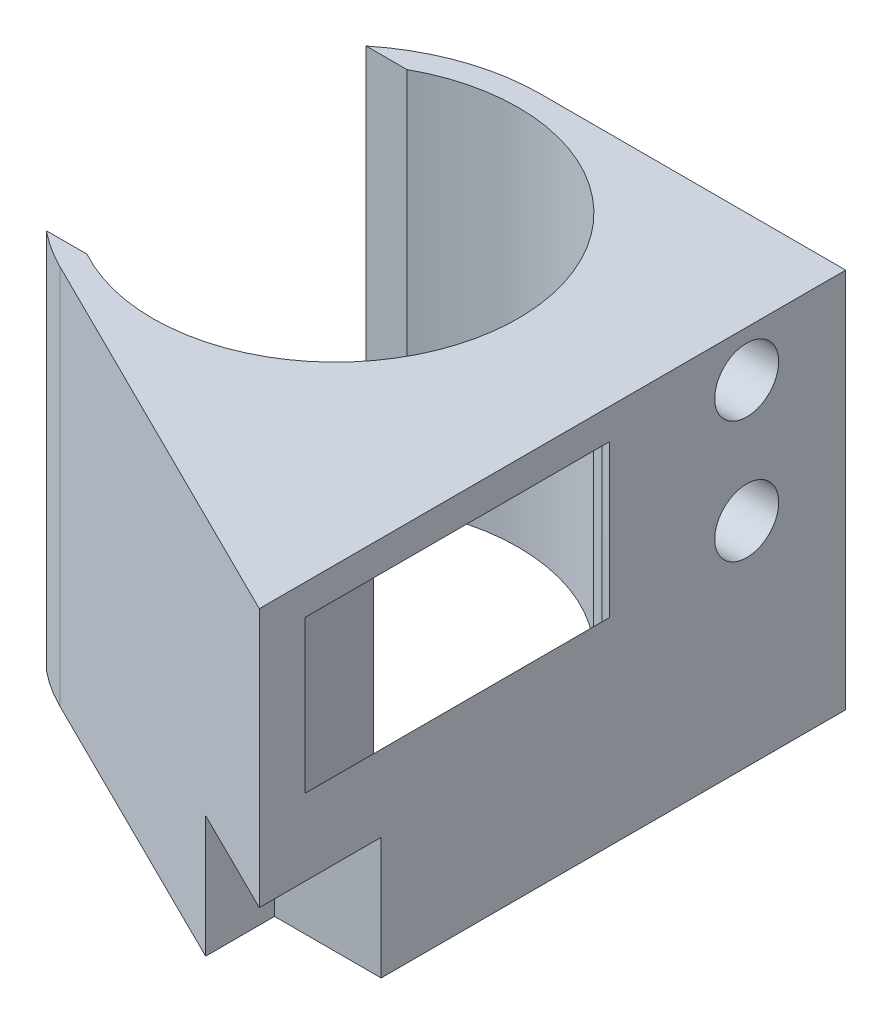
SolidWorks part; units mm, degrees
ref_plane "Front Plane" through (0, 0, 0) normal (0, 0, 1) x (1, 0, 0)
ref_plane "Top Plane" through (0, 0, 0) normal (0, 1, 0) x (1, 0, 0)
ref_plane "Right Plane" through (0, 0, 0) normal (1, 0, 0) x (0, 0, -1)
sketch "Sketch1" plane through (0, 0, 0) normal (0, 1, 0) x (1, 0, 0)
  line L0 (0, 13.5) -> (20, 13.5)
  line L1 (20, 13.5) -> (20, -25)
  line L2 (20, -25) -> (-6.0026, -12.0921)
  line L3 (0, 0) -> (20, 0) construction
  line L4 (20, 0) -> (20, -25) construction
  circle A0 centre (0, 0) radius 12
  arc A1 (0, 13.5) -> (-6.0026, -12.0921) centre (0, 0) ccw
  dimension "D1" = 24
  dimension "D2" = 27
  dimension "D3" = 20
  dimension "D4" = 25
extrude "Boss-Extrude1" add sketch "Sketch1" along normal blind 25
sketch "Sketch2" plane through (20, 0, 0) normal (1, 0, 0) x (0, 0, -1)
  line L0 (-25, 25) -> (-25, 0) construction
  line L1 (-22, 23) -> (-2, 23)
  line L2 (-22, 23) -> (-22, 13)
  line L3 (-22, 13) -> (-2, 13)
  line L4 (-2, 23) -> (-2, 13)
  line L5 (-25, 0) -> (13.5, 0) construction
  dimension "D1" = 3
  dimension "D2" = 10
  dimension "D3" = 20
  dimension "D4" = 13
ref_plane "Plane1" through (10, 0, 0) normal (1, 0, 0) x (0, 0, -1)
sketch "Sketch3" plane through (10, 0, 0) normal (1, 0, 0) x (0, 0, -1)
  line L0 (7.5, 12.5) -> (13.5, 12.5) construction
  line L1 (-7.5, 22.5) -> (7.5, 22.5)
  line L2 (-7.5, 22.5) -> (-7.5, 2.5)
  line L3 (-7.5, 2.5) -> (7.5, 2.5)
  line L4 (7.5, 22.5) -> (7.5, 2.5)
  line L5 (13.5, 25) -> (13.5, 0) construction
  point P5 (0, 22.5)
  dimension "D1" = 20
  dimension "D2" = 15
loft "Cut-Loft1" cut profiles "Sketch2", "Sketch3"
ref_plane "Plane2" through (0, 0, 17) normal (0, 0, 1) x (1, 0, 0)
sketch "Sketch4" plane through (0, 0, 17) normal (0, 0, 1) x (1, 0, 0)
  line L1 (20, 0) -> (13, 0)
  line L2 (20, 0) -> (20, 8)
  line L3 (20, 8) -> (13, 8)
  line L4 (13, 0) -> (13, 8)
  dimension "D1" = 7
  dimension "D2" = 8
extrude "Cut-Extrude2" cut sketch "Sketch4" along normal through all
sketch "Sketch5" plane through (0, 25, 0) normal (0, 1, 0) x (1, 0, 0)
  line L0 (20, 13.5) -> (0, 13.5) construction
  line L1 (-13.5, 10.5) -> (-5.8095, 10.5)
  line L2 (-13.5, 10.5) -> (-13.5, -10.5)
  line L3 (-13.5, -10.5) -> (-5.8095, -10.5)
  line L4 (-5.8095, 10.5) -> (-5.8095, -10.5)
  circle A0 centre (0, 0) radius 12 construction
  arc A1 (0, 13.5) -> (-6.0026, -12.0921) centre (0, 0) ccw construction
  point P13 (-5.8095, 0)
  dimension "D1" = 3
extrude "Cut-Extrude3" cut sketch "Sketch5" against normal through all
fillet "Fillet1" radius 2 2 edges
sketch "Sketch6" plane through (20, 0, 0) normal (1, 0, 0) x (0, 0, -1)
  line L0 (-17, 0) -> (13.5, 0) construction
  line L1 (13.5, 25) -> (-13.5, 25) construction
  line L2 (13.5, 25) -> (13.5, 0) construction
  line L3 (13.5, 0) -> (-13.5, 0) construction
  line L4 (-13.5, 25) -> (-13.5, 0) construction
  circle A0 centre (7, 22) radius 2.1
  circle A1 centre (7, 14) radius 2.1
  point P8 (0, 25)
  dimension "D1" = 4.2
  dimension "D2" = 4.2
  dimension "D3" = 8
  dimension "D4" = 7
  dimension "D5" = 3
extrude "Cut-Extrude4" cut sketch "Sketch6" against normal blind 4
